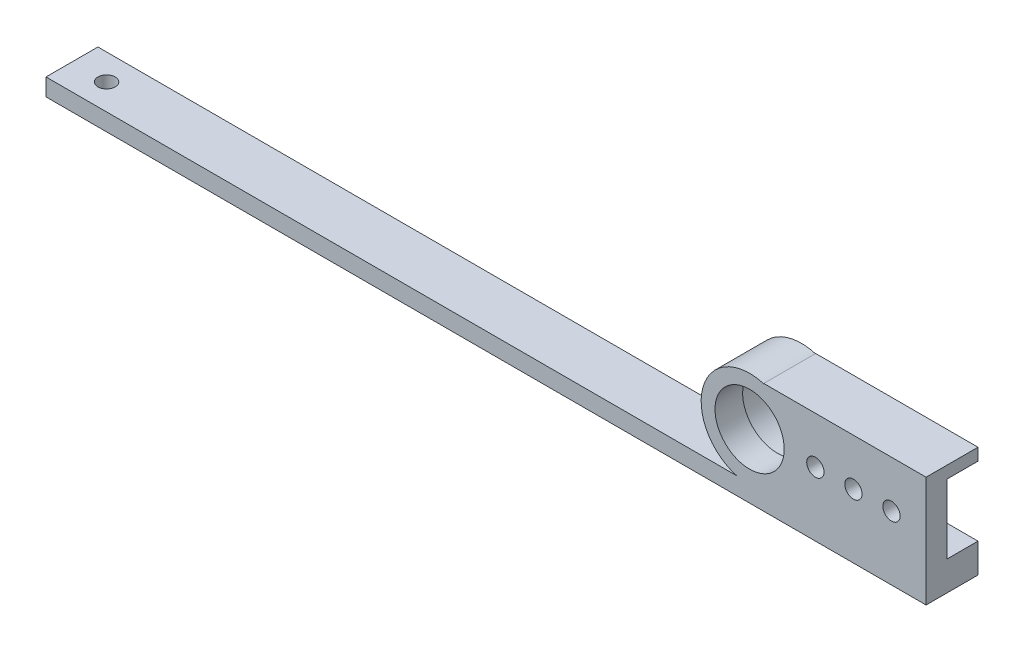
SolidWorks part; units mm, degrees
ref_plane "前视基准面" through (0, 0, 0) normal (0, 0, 1) x (1, 0, 0)
ref_plane "上视基准面" through (0, 0, 0) normal (0, 1, 0) x (1, 0, 0)
ref_plane "右视基准面" through (0, 0, 0) normal (1, 0, 0) x (0, 0, -1)
sketch "草图1" plane through (0, 0, 0) normal (0, 0, 1) x (1, 0, 0)
  line L1 (20, -10) -> (-20, -10)
  line L2 (20, -10) -> (20, 10)
  line L3 (20, 10) -> (-20, 10)
  line L4 (-20, -10) -> (-20, 10)
  line L5 (20, -10) -> (-20, 10) construction
  line L6 (20, 10) -> (-20, -10) construction
  point P0 (0, 0)
  dimension "D1" = 40
  dimension "D2" = 20
extrude "凸台-拉伸1" add sketch "草图1" along normal blind 6
sketch "草图2" plane through (0, 0, 6) normal (0, 0, 1) x (1, 0, 0)
  line L0 (20, -10) -> (20, 10) construction
  circle A0 centre (10, 0) radius 2.5
  circle A1 centre (-1, 0) radius 2.5
  circle A2 centre (-12, 0) radius 2.5
  dimension "D1" = 10
  dimension "D2" = 5
  dimension "D3" = 3
extrude "切除-拉伸1" cut sketch "草图2" against normal through all
sketch "草图3" plane through (0, 0, 6) normal (0, 0, 1) x (1, 0, 0)
  line L0 (20, 13.5) -> (20, 10)
  line L1 (20, -13.5) -> (-26.894, -13.5)
  line L3 (20, 13.5) -> (-26.894, 13.5)
  line L4 (-20, 10) -> (-20, -10)
  line L5 (-20, -10) -> (20, -10)
  line L6 (20, -10) -> (20, 10)
  line L7 (20, 10) -> (-20, 10)
  line L8 (-20, 10) -> (-20, -10)
  line L9 (-20, -10) -> (20, -10)
  line L10 (20, -10) -> (20, 10)
  line L11 (20, 10) -> (-20, 10)
  line L12 (-26.894, -13.5) -> (-26.894, 13.5)
  line L13 (20, -10.0394) -> (-26.894, 13.5) construction
  line L14 (20, 10.0394) -> (-26.894, -13.5) construction
  line L15 (20, -10) -> (20, -13.5)
  circle A0 centre (-31, 0) radius 11
  circle A1 centre (-31, 0) radius 14
  point P2 (0, 0)
  line M10 (-20, 10) -> (-20, -10)
  line M11 (-20, -10) -> (20, -10)
  line M13 (20, 10) -> (-20, 10)
  dimension "D3" = 22
  dimension "D4" = 28
  dimension "D2" = 3.5
  dimension "D1" = 0
extrude "凸台-拉伸2" add sketch "草图3" against normal blind 15 contours L3 A1 L1 L12 A0 | A1 L1 L15 M11 M10 | L1 A1 L8 A0 L12 | L8 A1 L3 L12 A0 | L8 A1 | A1 L0 L3 M10 M13 region at (-1.9449, 11.7771, 6) region at (-1.9449, -11.7771, 6) region at (-23.0173, 9.0328, 6) region at (-27.2274, 11.7946, 6) region at (-18.7882, 0, 6) region at (-23.0173, -9.0328, 6)
sketch "草图5" plane through (0, 0, 6) normal (0, 0, 1) x (1, 0, 0)
  circle A0 centre (-31, 0) radius 10
  circle A1 centre (-31, 0) radius 11 construction
  circle A2 centre (-31, 0) radius 11
  dimension "D1" = 20
extrude "凸台-拉伸3" add sketch "草图5" against normal blind 8
sketch "草图6" plane through (0, 0, 6) normal (0, 0, 1) x (1, 0, 0)
  circle A0 centre (-31, 0) radius 8.5
  circle A1 centre (-31, 0) radius 10 construction
  circle A2 centre (-31, 0) radius 10
  dimension "D1" = 17
sketch "草图8" plane through (0, 0, 6) normal (0, 0, 1) x (1, 0, 0)
  line L0 (20, -13.5) -> (20, 13.5) construction
  line L1 (20, -13.5) -> (-26.894, -13.5) construction
  line L2 (20, 13.5) -> (-26.894, 13.5) construction
  line L3 (20, -13.5) -> (20, 13.5)
  line L4 (20, -13.5) -> (-26.894, -13.5)
  line L5 (20, 13.5) -> (-26.894, 13.5)
  line L6 (-45, -14) -> (-26.894, -13.5)
  line L7 (-45, -14) -> (-239, -14)
  line L8 (-45, -14) -> (-45, 14)
  line L9 (-45, 14) -> (-239, 14)
  line L10 (-239, -14) -> (-239, 14)
  line L11 (-45, -14) -> (-239, 14) construction
  line L12 (-45, 14) -> (-239, -14) construction
  line L13 (-45, 14) -> (-26.894, 13.3843)
  line L14 (-12, 0) -> (-31, 0)
  arc A0 (-26.894, 13.3843) -> (-26.894, -13.3843) centre (-31, 0) ccw construction
  arc A1 (-26.894, 13.3843) -> (-26.894, -13.3843) centre (-31, 0) ccw
  point P6 (-142, 0)
  dimension "D1" = 28
  dimension "D2" = 194
  dimension "D3" = 14
sketch "草图9" plane through (0, -13.5, 0) normal (0, -1, 0) x (1, 0, 0)
  circle A0 centre (10.5344, 0) radius 5.2388
sketch "草图10" plane through (20, 0, 0) normal (1, 0, 0) x (0, 0, -1)
  line L1 (9, -13.5) -> (-6, -13.5)
  line L2 (9, -13.5) -> (9, -18.5)
  line L3 (9, -18.5) -> (-6, -18.5)
  line L4 (-6, -13.5) -> (-6, -18.5)
  dimension "D1" = 5
extrude "凸台-拉伸4" add sketch "草图10" against normal blind 500
sketch "草图11" plane through (0, 0, -9) normal (0, 0, -1) x (-1, 0, 0)
  line L1 (22.0371, -11.3638) -> (33.5283, -11.3638)
  line L2 (22.0371, -11.3638) -> (22.0371, -16.4864)
  line L3 (22.0371, -16.4864) -> (33.5283, -16.4864)
  line L4 (33.5283, -11.3638) -> (33.5283, -16.4864)
extrude "凸台-拉伸5" add sketch "草图11" against normal through all
sketch "草图12" plane through (0, -18.5, 0) normal (0, -1, 0) x (1, 0, 0)
  line L0 (-234.3163, -14.8999) -> (-234.3163, 6)
  line L1 (-234.3163, 118.5858) -> (-234.3163, -251.4142) construction
  line L2 (-234.3163, -14.8999) -> (-86.5711, -14.8999) construction
  line L3 (-480, 6) -> (20, 6) construction
sketch "草图13" plane through (0, -18.5, 0) normal (0, -1, 0) x (1, 0, 0)
  line L1 (-234.3163, -14.8999) -> (-490.0472, -14.8999)
  line L2 (-234.3163, -14.8999) -> (-234.3163, 14.9475)
  line L3 (-234.3163, 14.9475) -> (-490.0472, 14.9475)
  line L4 (-490.0472, -14.8999) -> (-490.0472, 14.9475)
extrude "切除-拉伸2" cut sketch "草图13" against normal through all
sketch "草图14" plane through (0, -18.5, 0) normal (0, -1, 0) x (1, 0, 0)
  line L0 (-234.3163, 6) -> (-234.3163, -9) construction
  line L1 (-234.3163, -1.5) -> (-224.3163, -1.5) construction
  circle A0 centre (-224.3163, -1.5) radius 2.5
  dimension "D1" = 5
  dimension "D2" = 10
extrude "切除-拉伸3" cut sketch "草图14" against normal through all
